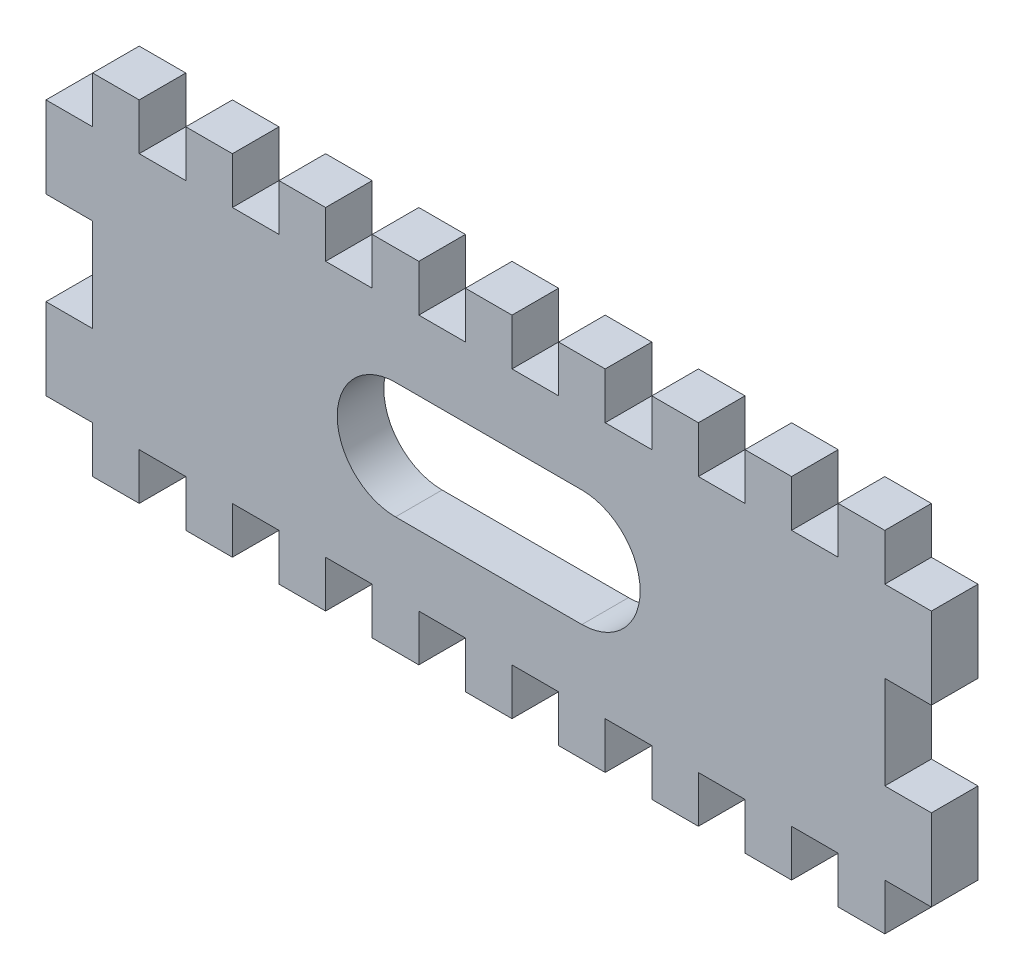
SolidWorks part; units mm, degrees
ref_plane "Front Plane" through (0, 0, 0) normal (0, 0, 1) x (1, 0, 0)
ref_plane "Top Plane" through (0, 0, 0) normal (0, 1, 0) x (1, 0, 0)
ref_plane "Right Plane" through (0, 0, 0) normal (1, 0, 0) x (0, 0, -1)
sketch "Sketch1" plane through (0, 0, 0) normal (0, 0, 1) x (1, 0, 0)
  line L1 (-60.325, -17.4625) -> (60.325, -17.4625)
  line L2 (-60.325, -17.4625) -> (-60.325, 17.4625)
  line L3 (-60.325, 17.4625) -> (60.325, 17.4625)
  line L4 (60.325, -17.4625) -> (60.325, 17.4625)
  line L5 (-60.325, -17.4625) -> (60.325, 17.4625) construction
  line L6 (-60.325, 17.4625) -> (60.325, -17.4625) construction
  point P0 (0, 0)
  dimension "D1" = 34.925
  dimension "D2" = 120.65
extrude "Mass" add sketch "Sketch1" along normal blind 6.35
sketch "Bore Pattern" plane through (0, 0, 6.35) normal (0, 0, 1) x (1, 0, 0)
  line L0 (60.325, 17.4625) -> (-60.325, -17.4625) construction
  line L1 (-38.1, 0) -> (38.1, 0) construction
  point P8 (0, 0)
  dimension "D2" = 76.2
sketch "Sketch3" plane through (0, 0, 0) normal (0, 0, -1) x (-1, 0, 0)
  line L0 (0, 0) -> (0, 17.4625) construction
  line L2 (0, 0) -> (0, -17.4625) construction
  line L4 (60.325, -17.4625) -> (-60.325, -17.4625) construction
  line L5 (3.175, 11.1125) -> (-3.175, 11.1125)
  line L6 (3.175, 11.1125) -> (3.175, 23.8125)
  line L7 (3.175, 23.8125) -> (-3.175, 23.8125)
  line L8 (-3.175, 11.1125) -> (-3.175, 23.8125)
  line L9 (3.175, 11.1125) -> (-3.175, 23.8125) construction
  line L10 (3.175, 23.8125) -> (-3.175, 11.1125) construction
  line L11 (3.175, -23.8125) -> (-3.175, -23.8125)
  line L12 (3.175, -23.8125) -> (3.175, -11.1125)
  line L13 (3.175, -11.1125) -> (-3.175, -11.1125)
  line L14 (-3.175, -23.8125) -> (-3.175, -11.1125)
  line L15 (3.175, -23.8125) -> (-3.175, -11.1125) construction
  line L16 (3.175, -11.1125) -> (-3.175, -23.8125) construction
  line L18 (-60.325, 17.4625) -> (60.325, 17.4625) construction
  dimension "D1" = 12.7
  dimension "D2" = 6.35
extrude "Top Tooth" add sketch "Sketch3" against normal up to surface (6.35 mm away) up to face at (0, 0, 6.35)
pattern_linear "Top Puzzle" count 5 spacing 12.7 along (-1, 0, 0) count 5 spacing 12.7 along (1, 0, 0) of "Top Tooth"
sketch "Sketch4" plane through (0, 0, 6.35) normal (0, 0, 1) x (1, 0, 0)
  line L0 (0, 0) -> (60.325, 0) construction
  line L2 (60.325, -17.4625) -> (60.325, 17.4625) construction
  line L3 (0, 0) -> (-60.325, 0) construction
  line L4 (53.975, -6.35) -> (66.675, -6.35)
  line L5 (53.975, -6.35) -> (53.975, 6.35)
  line L6 (53.975, 6.35) -> (66.675, 6.35)
  line L7 (66.675, -6.35) -> (66.675, 6.35)
  line L8 (53.975, -6.35) -> (66.675, 6.35) construction
  line L9 (53.975, 6.35) -> (66.675, -6.35) construction
  line L11 (-60.325, 17.4625) -> (-60.325, -17.4625) construction
  line L13 (-53.975, -6.35) -> (-66.675, -6.35)
  line L14 (-53.975, -6.35) -> (-53.975, 6.35)
  line L15 (-53.975, 6.35) -> (-66.675, 6.35)
  line L16 (-66.675, -6.35) -> (-66.675, 6.35)
  line L17 (-53.975, -6.35) -> (-66.675, 6.35) construction
  line L18 (-53.975, 6.35) -> (-66.675, -6.35) construction
  dimension "D1" = 12.7
  dimension "D2" = 12.7
extrude "Side Tooth" cut sketch "Sketch4" against normal through all
sketch "Sketch5" plane through (0, 0, 0) normal (0, 0, -1) x (-1, 0, 0)
  line L0 (-12.7, 0) -> (12.7, 0) construction
  line L1 (-12.7, 7.9375) -> (12.7, 7.9375)
  line L2 (-12.7, -7.9375) -> (12.7, -7.9375)
  arc A0 (-12.7, 7.9375) -> (-12.7, -7.9375) centre (-12.7, 0) ccw
  arc A1 (12.7, -7.9375) -> (12.7, 7.9375) centre (12.7, 0) ccw
  point P2 (0, 0)
  dimension "D2" = 7.9375
  dimension "D1" = 25.4
extrude "Lighten" cut sketch "Sketch5" against normal through all
